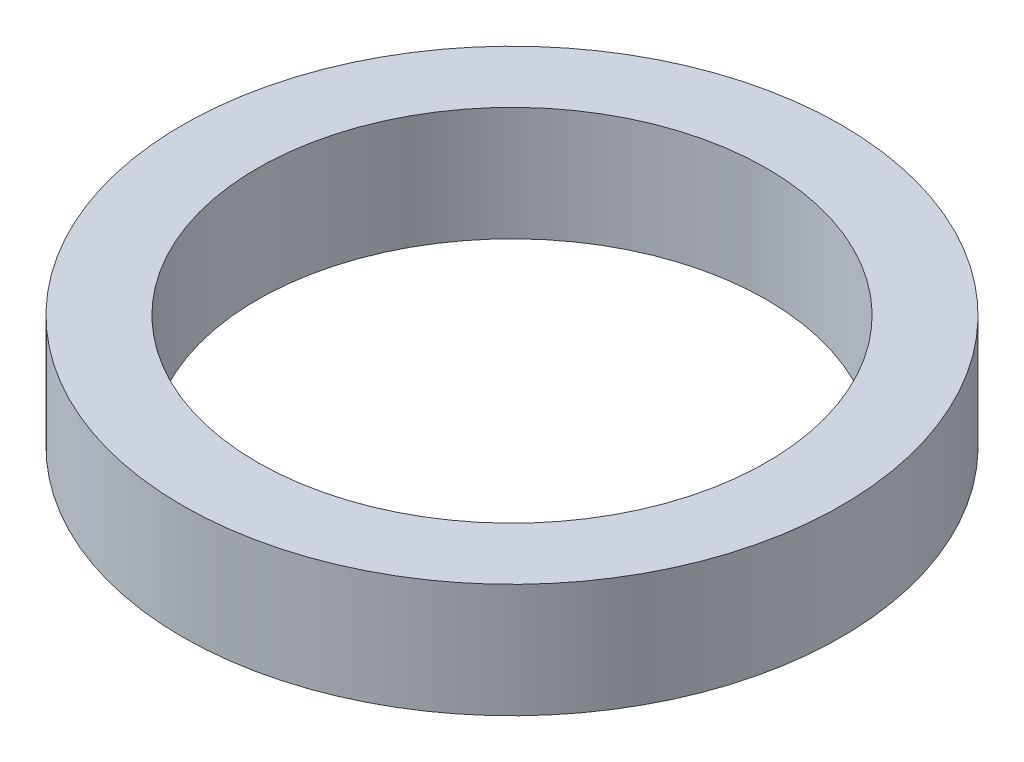
SolidWorks part; units mm, degrees
ref_plane "Front Plane" through (0, 0, 0) normal (0, 0, 1) x (1, 0, 0)
ref_plane "Top Plane" through (0, 0, 0) normal (0, 1, 0) x (1, 0, 0)
ref_plane "Right Plane" through (0, 0, 0) normal (1, 0, 0) x (0, 0, -1)
sketch "Sketch1" plane through (0, 0, 0) normal (0, 1, 0) x (1, 0, 0)
  circle A0 centre (0, 0) radius 55
  dimension "FLANGE_OD" = 110
extrude "Boss-Extrude1" add sketch "Sketch1" along normal blind 19
sketch "Sketch2" plane through (0, 0, 0) normal (0, 1, 0) x (1, 0, 0)
  circle A0 centre (0, 0) radius 42.5
  dimension "BORE_D" = 85
extrude "Cut-Extrude1" cut sketch "Sketch2" along normal through all
sketch "Sketch3" plane through (0, 19, 0) normal (0, 1, 0) x (1, 0, 0)
  circle A0 centre (0, 0) radius 24.6899 construction
  circle A1 centre (-24.6899, 0) radius 1.9022
  dimension "BOLT_D" = 3.8044
  dimension "BOLT_PCD" = 49.3798
extrude "Cut-Extrude2" cut sketch "Sketch3" against normal blind 16.0384 rebuild error yes
pattern_circular "CirPattern1" count 3 over 360 rebuild error yes
